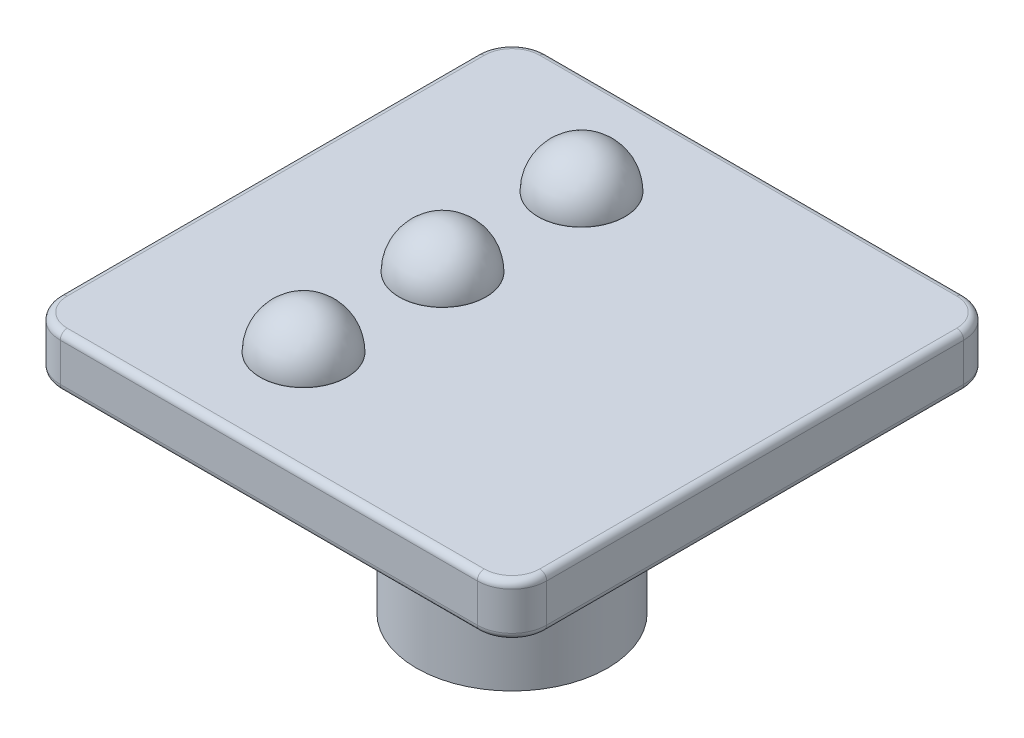
SolidWorks part; units mm, degrees
ref_plane "Front Plane" through (0, 0, 0) normal (0, 0, 1) x (1, 0, 0)
ref_plane "Top Plane" through (0, 0, 0) normal (0, 1, 0) x (1, 0, 0)
ref_plane "Right Plane" through (0, 0, 0) normal (1, 0, 0) x (0, 0, -1)
sketch "Sketch1" plane through (0, 0, 0) normal (0, 1, 0) x (1, 0, 0)
  line L1 (-7.3247, 4.3967) -> (4.6753, 4.3967)
  line L2 (-8.3247, 3.3967) -> (-8.3247, -8.6033)
  line L3 (-7.3247, -9.6033) -> (4.6753, -9.6033)
  line L4 (5.6753, 3.3967) -> (5.6753, -8.6033)
  arc A0 (-8.3247, -8.6033) -> (-7.3247, -9.6033) centre (-7.3247, -8.6033) ccw
  arc A1 (4.6753, -9.6033) -> (5.6753, -8.6033) centre (4.6753, -8.6033) ccw
  arc A2 (4.6753, 4.3967) -> (5.6753, 3.3967) centre (4.6753, 3.3967) cw
  arc A3 (-7.3247, 4.3967) -> (-8.3247, 3.3967) centre (-7.3247, 3.3967) ccw
  point P8 (5.6753, -9.6033)
  point P11 (5.6753, 4.3967)
  point P14 (-8.3247, 4.3967)
  dimension "D3" = 1
  dimension "D1" = 14
  dimension "D2" = 14
extrude "Boss-Extrude1" add sketch "Sketch1" along normal blind 1.5
sketch "Sketch2" plane through (0, 0, 0) normal (0, -1, 0) x (1, 0, 0)
  line L0 (-7.3247, 9.6033) -> (4.6753, 9.6033) construction
  line L1 (5.6753, 8.6033) -> (5.6753, -3.3967) construction
  line L2 (-1.3247, -4.3967) -> (-1.3247, 9.6033) construction
  line L3 (-8.3247, 2.6033) -> (5.6753, 2.6033) construction
  line L4 (-8.3247, -3.3967) -> (-8.3247, 8.6033) construction
  circle A0 centre (-1.3247, 2.6033) radius 2.75
  dimension "D1" = 7
  dimension "D2" = 7
extrude "Boss-Extrude2" add sketch "Sketch2" along normal blind 6
sketch "Sketch3" plane through (0, -6, 0) normal (0, -1, 0) x (1, 0, 0)
  line L0 (-1.3247, 5.3533) -> (-1.3247, -0.1467) construction
  line L1 (-3.3247, 3.1533) -> (0.6753, 3.1533)
  line L2 (-3.3247, 3.1533) -> (-3.3247, 2.0533)
  line L3 (-3.3247, 2.0533) -> (0.6753, 2.0533)
  line L4 (0.6753, 3.1533) -> (0.6753, 2.0533)
  line L5 (-1.8747, 4.6033) -> (-0.7747, 4.6033)
  line L6 (-1.8747, 4.6033) -> (-1.8747, 0.6033)
  line L7 (-1.8747, 0.6033) -> (-0.7747, 0.6033)
  line L8 (-0.7747, 4.6033) -> (-0.7747, 0.6033)
  line L9 (-4.0747, 2.6033) -> (1.4253, 2.6033) construction
  circle A3 centre (-1.3247, 2.6033) radius 2.75 construction
  circle A4 centre (-1.3247, 2.6033) radius 2.75 construction
  dimension "D7" = 0.55
  dimension "D1" = 4
  dimension "D2" = 1.1
  dimension "D3" = 1.1
  dimension "D4" = 4
  dimension "D5" = 2
  dimension "D6" = 2
  dimension "D8" = 0.55
extrude "Cut-Extrude1" cut sketch "Sketch3" against normal blind 6 contours L8 L5 L6 L1 | L1 L8 L3 L4 | L8 L1 L6 L3 | L6 L1 L2 L3 | L8 L3 L6 L7 region at (-2.5997, -6, 2.6033) region at (-1.3247, -6, 3.8783) region at (-1.3247, -6, 2.6033) region at (-0.0497, -6, 2.6033) region at (-1.3247, -6, 1.3283)
chamfer "Chamfer1" distance 0.3 angle 45 12 edges at (-1.3247, -6, 0.6033) (-1.8747, -6, 1.3283) (-2.5997, -6, 2.0533) (-3.3247, -6, 2.6033) (-2.5997, -6, 3.1533) (-0.7747, -6, 1.3283) (-0.0497, -6, 2.0533) (0.6753, -6, 2.6033) (-0.0497, -6, 3.1533) (-0.7747, -6, 3.8783) (-1.3247, -6, 4.6033) (-1.8747, -6, 3.8783)
fillet "Fillet1" radius 1 1 edges at (-1.3247, 0, -0.1467)
sketch "Sketch4" plane through (0, 1.5, 0) normal (0, 1, 0) x (1, 0, 0)
  line L0 (-1.3247, 4.3967) -> (-1.3247, -9.6033) construction
  line L1 (4.6753, 4.3967) -> (-7.3247, 4.3967) construction
  line L2 (-7.3247, -9.6033) -> (4.6753, -9.6033) construction
  line L3 (5.6753, -2.6033) -> (-8.3247, -2.6033) construction
  line L4 (-8.3247, 3.3967) -> (-8.3247, -8.6033) construction
  line L5 (5.6753, -8.6033) -> (5.6753, 3.3967) construction
  line L6 (-3.3247, 4.3967) -> (-3.3247, -9.6033) construction
  line L7 (0.6753, 4.3967) -> (0.6753, -9.6033) construction
  line L8 (-8.3247, 1.3967) -> (5.6753, 1.3967) construction
  line L9 (5.6753, -6.6033) -> (-8.3247, -6.6033) construction
  circle A0 centre (-3.3247, 1.3967) radius 1.25
  circle A2 centre (-3.3247, -2.6033) radius 1.25
  circle A3 centre (-3.3247, -6.6033) radius 1.25
  dimension "D1" = 4
  dimension "D2" = 4
  dimension "D3" = 2
  dimension "D4" = 2
extrude "Boss-Extrude3" add sketch "Sketch4" along normal blind 0.01
dome "Dome1" faces to dome 1 distance 1.25 reverse direction no elliptical dome no face at (-3.3247, 1.51, -0.1467) parameters "D1"=1.25
dome "Dome3" faces to dome 1 distance 1.25 reverse direction no elliptical dome no face at (-3.3247, 1.51, 3.8533) parameters "D1"=1.25
dome "Dome5" faces to dome 1 distance 1.25 reverse direction no elliptical dome no face at (-3.3247, 1.51, 7.8533) parameters "D1"=1.25
fillet "Fillet3" radius 0.2 16 edges at (5.3824, 1.5, -4.1038) (5.6753, 1.5, 2.6033) (5.3824, 1.5, 9.3104) (-1.3247, 1.5, 9.6033) (-8.0318, 1.5, 9.3104) (-8.0318, 1.5, -4.1038) (-8.3247, 1.5, 2.6033) (-1.3247, 1.5, -4.3967) (5.3824, 0, 9.3104) (5.6753, 0, 2.6033) (5.3824, 0, -4.1038) (-1.3247, 0, -4.3967) (-8.0318, 0, -4.1038) (-8.3247, 0, 2.6033) (-8.0318, 0, 9.3104) (-1.3247, 0, 9.6033)
